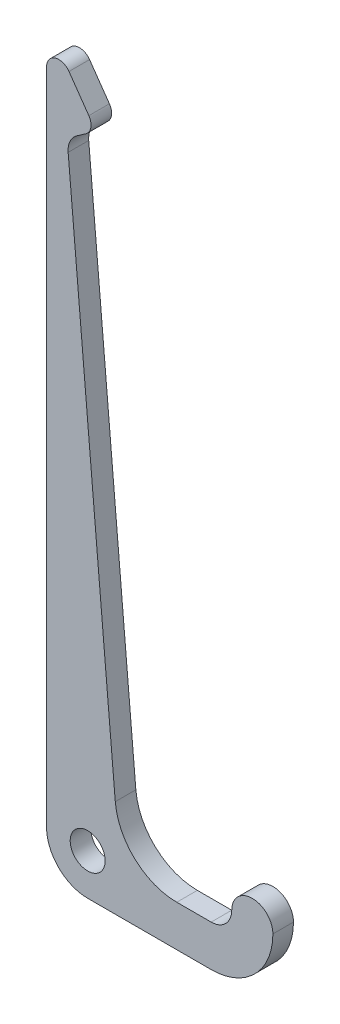
SolidWorks part; units mm, degrees
ref_plane "Спереди" through (0, 0, 0) normal (0, 0, 1) x (1, 0, 0)
ref_plane "Сверху" through (0, 0, 0) normal (0, 1, 0) x (1, 0, 0)
ref_plane "Справа" through (0, 0, 0) normal (1, 0, 0) x (0, 0, -1)
sketch "Эскиз1" plane through (0, 0, 0) normal (0, 0, 1) x (1, 0, 0)
  line L0 (0, 113.8462) -> (0, -91.2821) construction
  line L1 (-10, -51.7949) -> (-10, 108.2051)
  line L2 (-4.5425, 109.9259) -> (0.2793, 103.0396)
  line L3 (-0.4575, 98.8614) -> (-2.6353, 97.3365)
  line L4 (-4.7484, 92.8049) -> (6.7045, -38.1022)
  line L6 (0, -61.7949) -> (45, -61.7949)
  line L7 (45, -61.7949) -> (45, -46.7949)
  line L9 (21.6474, -51.7949) -> (35, -51.7949)
  line L10 (35, -51.7949) -> (35, -46.7949)
  arc A0 (-10, -51.7949) -> (0, -61.7949) centre (0, -51.7949) ccw
  arc A1 (-4.5425, 109.9259) -> (-10, 108.2051) centre (-7, 108.2051) ccw
  arc A2 (45, -46.7949) -> (35, -46.7949) centre (40, -46.7949) ccw
  arc A3 (21.6474, -51.7949) -> (6.7045, -38.1022) centre (21.6474, -36.7949) cw
  arc A4 (0.2793, 103.0396) -> (-0.4575, 98.8614) centre (-2.1782, 101.3189) cw
  arc A5 (-2.6353, 97.3365) -> (-4.7484, 92.8049) centre (0.2326, 93.2407) ccw
  circle A6 centre (0, -51.7949) radius 4.25
  point P25 (2, 100.5821)
  dimension "D1" = 20
  dimension "D2" = 6
  dimension "D8" = 15
  dimension "D9" = 10
  dimension "D7" = 3
  dimension "D10" = 5
  dimension "D4" = 8.5
  dimension "D3" = 35
  dimension "D5" = 12
  dimension "D6" = 55
extrude "Бобышка-Вытянуть1" add sketch "Эскиз1" along normal blind 5
fillet "Скругление1" radius 5 1 edges at (35, -51.7949, 2.5)
fillet "Скругление2" radius 15 1 edges at (45, -61.7949, 2.5)
